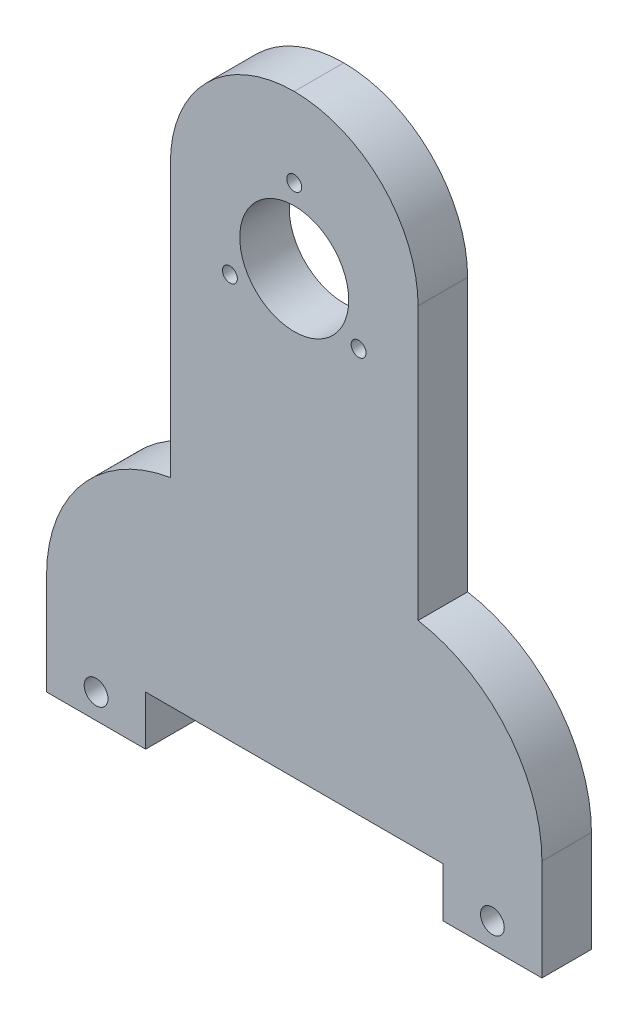
SolidWorks part; units mm, degrees
ref_plane "Front Plane" through (0, 0, 0) normal (0, 0, 1) x (1, 0, 0)
ref_plane "Top Plane" through (0, 0, 0) normal (0, 1, 0) x (1, 0, 0)
ref_plane "Right Plane" through (0, 0, 0) normal (1, 0, 0) x (0, 0, -1)
sketch "Sketch2" plane through (0, 0, 0) normal (0, 0, 1) x (1, 0, 0)
  line L1 (-50, -65) -> (50, -65)
  line L2 (-50, -65) -> (-50, 65)
  line L3 (-50, 65) -> (50, 65)
  line L4 (50, -65) -> (50, 65)
  line L5 (-50, -65) -> (50, 65) construction
  line L6 (-50, 65) -> (50, -65) construction
  point P0 (0, 0)
  dimension "D1" = 130
  dimension "D2" = 100
extrude "Boss-Extrude1" add sketch "Sketch2" along normal blind 10
sketch "Sketch4" plane through (0, 0, 10) normal (0, 0, 1) x (1, 0, 0)
  line L0 (-50, -65) -> (-30, -65) construction
  line L1 (-50, -65) -> (50, -65) construction
  line L2 (50, -65) -> (30, -65) construction
  line L3 (0, 65) -> (0, 0) construction
  line L4 (-30, -65) -> (30, -65)
  line L5 (-30, -65) -> (-30, -55)
  line L6 (-30, -55) -> (30, -55)
  line L7 (30, -65) -> (30, -55)
  line L8 (-50, 65) -> (-25, 65)
  line L9 (-50, 65) -> (-50, -15)
  line L10 (-50, -15) -> (-25, -15)
  line L11 (-25, 65) -> (-25, -15)
  line L12 (50, 65) -> (-50, 65) construction
  line L13 (50, -15) -> (25, -15)
  line L14 (25, 65) -> (25, -15)
  line L15 (50, 65) -> (25, 65)
  line L16 (50, 65) -> (50, -15)
  dimension "D1" = 20
  dimension "D2" = 20
  dimension "D3" = 10
  dimension "D4" = 60
  dimension "D5" = 80
  dimension "D6" = 25
extrude "Cut-Extrude1" cut sketch "Sketch4" against normal blind 55
sketch "Sketch6" plane through (0, 0, 0) normal (0, 0, -1) x (-1, 0, 0)
  line L1 (-30, -55) -> (30, -55)
  line L2 (-30, -55) -> (-30, -49)
  line L3 (-30, -49) -> (30, -49)
  line L4 (30, -55) -> (30, -49)
  dimension "D1" = 6
  dimension "D2" = 60
extrude "Boss-Extrude2" add sketch "Sketch6" along normal blind 15
sketch "Sketch10" plane through (0, 0, 10) normal (0, 0, 1) x (1, 0, 0)
  line L0 (-40, -65) -> (-40, -60) construction
  line L1 (-50, -65) -> (-30, -65) construction
  line L2 (40, -65) -> (40, -60) construction
  line L3 (30, -65) -> (50, -65) construction
  circle A0 centre (-40, -60) radius 2.4
  circle A1 centre (40, -60) radius 2.4
  dimension "D2" = 4.8
  dimension "D3" = 4.8
  dimension "D1" = 5
  dimension "D4" = 5
extrude "Cut-Extrude3" cut sketch "Sketch10" against normal blind 15
fillet "Fillet6" radius 30 1 edges at (50, -15, 5)
fillet "Fillet7" radius 30 1 edges at (-50, -15, 5)
sketch "Sketch12" plane through (0, 0, 0) normal (1, 0, 0) x (0, 0, -1)
  line L0 (15, -49) -> (0, 0)
rib "Rib9" sketch "Sketch12" sketch "Sketch12" thickness 6 extrusion direction parallel to sketch draft on no parameters "D1"=6
sketch "Sketch13" plane through (-30, 0, 0) normal (-1, 0, 0) x (0, 0, 1)
  line L0 (-15, -49) -> (0, -25.8796)
rib "Rib10" sketch "Sketch13" sketch "Sketch13" thickness 6 extrusion direction parallel to sketch draft on no parameters "D1"=6
mirror "Mirror4" about plane through (0, 0, 0) normal (1, 0, 0) of "Rib10"
sketch "Sketch14" plane through (0, -49, 0) normal (0, 1, 0) x (1, 0, 0)
  line L0 (-13.5, 0) -> (-13.5, 7.5) construction
  line L1 (-24, 0) -> (-3, 0) construction
  line L2 (13.5, 0) -> (13.5, 7.5) construction
  line L3 (3, 0) -> (24, 0) construction
  circle A0 centre (-13.5, 7.5) radius 2
  circle A1 centre (13.5, 7.5) radius 2
  dimension "D2" = 4
  dimension "D4" = 4
  dimension "D1" = 7.5
  dimension "D3" = 7.5
extrude "Cut-Extrude4" cut sketch "Sketch14" against normal blind 15
fillet "Fillet8" radius 25 2 edges at (25, 65, 5) (-25, 65, 5)
sketch "Sketch15" plane through (0, 0, 10) normal (0, 0, 1) x (1, 0, 0)
  line L0 (-30, -65) -> (30, -65) construction
  line L1 (30, -65) -> (0, -65) construction
  line L2 (0, -65) -> (0, 34) construction
  circle A0 centre (0, 34) radius 11
  dimension "D2" = 22
  dimension "D1" = 99
extrude "Cut-Extrude5" cut sketch "Sketch15" against normal blind 15
sketch "Sketch17" plane through (0, 0, 10) normal (0, 0, 1) x (1, 0, 0)
  line L0 (0, 34) -> (0, 49) construction
  circle A0 centre (0, 49) radius 1.5
  circle A7 centre (12.9904, 26.5) radius 1.5
  circle A8 centre (-12.9904, 26.5) radius 1.5
  point P12 (-0.7217, 35.25)
  point P13 (0, 34)
  dimension "D2" = 3
  dimension "D1" = 15
  dimension "D3" = 3
extrude "Cut-Extrude6" cut sketch "Sketch17" against normal blind 15
